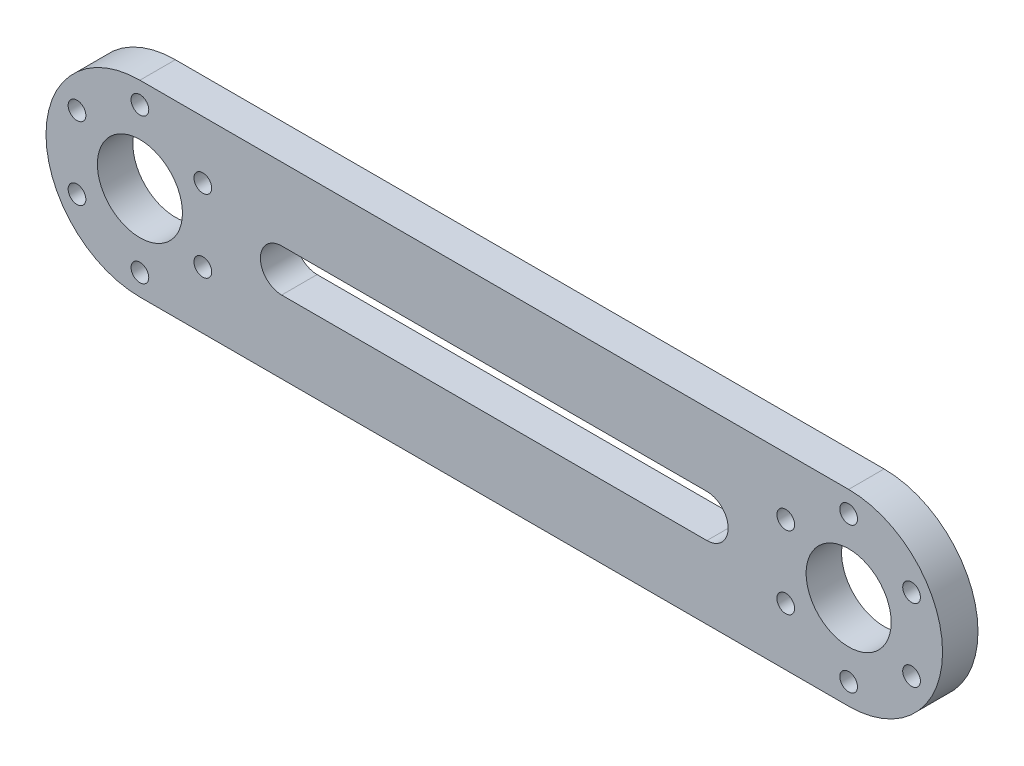
SolidWorks part; units mm, degrees
material "Wrought Stainless Steel"
ref_plane "Front Plane" through (0, 0, 0) normal (0, 0, 1) x (1, 0, 0)
ref_plane "Top Plane" through (0, 0, 0) normal (0, 1, 0) x (1, 0, 0)
ref_plane "Right Plane" through (0, 0, 0) normal (1, 0, 0) x (0, 0, -1)
sketch "Sketch1" plane through (0, 0, 0) normal (0, 0, 1) x (1, 0, 0)
  line L0 (0, 13.25) -> (100, 13.25)
  line L1 (0, -13.25) -> (100, -13.25)
  line L2 (50, 0) -> (50, -3)
  line L3 (50, 0) -> (50, 3)
  line L4 (20, 3) -> (80, 3)
  line L5 (20, -3) -> (80, -3)
  circle A0 centre (0, 0) radius 13.25
  circle A1 centre (100, 0) radius 13.25
  circle A2 centre (0, 0) radius 6
  circle A3 centre (100, 0) radius 6
  circle A4 centre (20, 0) radius 3
  circle A5 centre (80, 0) radius 3
  point P18 (50, 3)
  point P21 (50, -3)
extrude "Boss-Extrude1" add sketch "Sketch1" along normal blind 5 contours A0 A2 | A1 L0 A0 L1 A5 L5 A4 L4 | A1 A3 region at (50, 12.2155, 0) region at (9.1042, 9.1042, 0) region at (109.1042, 9.1042, 0)
sketch "Sketch2" plane through (0, 0, 5) normal (0, 0, 1) x (1, 0, 0)
  line L0 (0, 0) -> (8.8768, 5.125)
  line L1 (0, 0) -> (8.8768, -5.125)
  line L2 (0, 0) -> (-8.8768, 5.125)
  line L3 (0, 0) -> (-8.8768, -5.125)
  line L4 (0, 10.25) -> (0, -10.25)
  line L5 (50, 13.25) -> (50, -13.25) construction
  line L6 (0, 13.25) -> (100, 13.25) construction
  line L7 (0, -13.25) -> (100, -13.25) construction
  circle A0 centre (0, 0) radius 10.25
  circle A1 centre (0, 10.25) radius 1.25
  circle A2 centre (0, -10.25) radius 1.25
  circle A3 centre (8.8768, 5.125) radius 1.25
  circle A4 centre (8.8768, -5.125) radius 1.25
  circle A5 centre (-8.8768, 5.125) radius 1.25
  circle A6 centre (-8.8768, -5.125) radius 1.25
  circle A7 centre (100, -10.25) radius 1.25
  circle A8 centre (108.8768, -5.125) radius 1.25
  circle A9 centre (108.8768, 5.125) radius 1.25
  circle A10 centre (100, 10.25) radius 1.25
  circle A11 centre (91.1232, 5.125) radius 1.25
  circle A12 centre (91.1232, -5.125) radius 1.25
extrude "Cut-Extrude1" cut sketch "Sketch2" against normal through all contours A10 | A9 | A3 | A4 | A5 | A6 | A2 | A1 | A11 | A8 | A7 | A12 region at (108.8768, 5.125, 5) region at (100, 10.25, 5)
